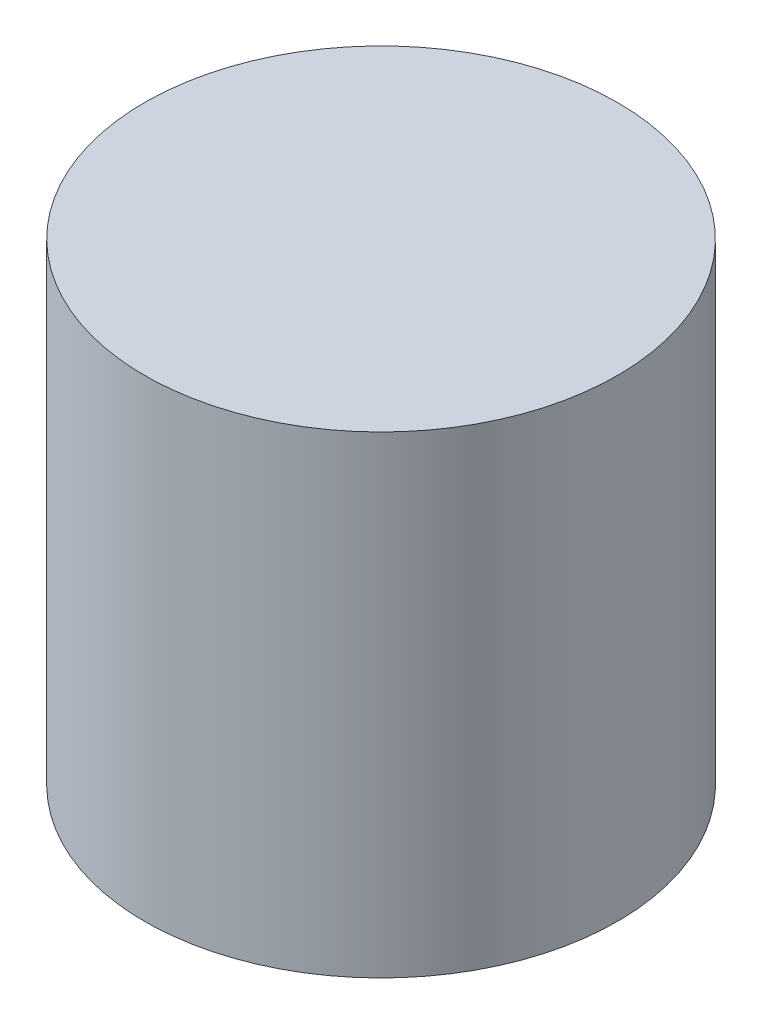
SolidWorks part; units mm, degrees
ref_plane "Front Plane" through (0, 0, 0) normal (0, 0, 1) x (1, 0, 0)
ref_plane "Top Plane" through (0, 0, 0) normal (0, 1, 0) x (1, 0, 0)
ref_plane "Right Plane" through (0, 0, 0) normal (1, 0, 0) x (0, 0, -1)
sketch "Sketch1" plane through (0, 0, 0) normal (0, 1, 0) x (1, 0, 0)
  circle A0 centre (0, 0) radius 38.1
  dimension "D1" = 76.2
extrude "Boss-Extrude1" add sketch "Sketch1" along normal blind 76.2
shell "Shell1" thickness 6.35
sketch "Sketch2" plane through (0, 0, 0) normal (0, -1, 0) x (1, 0, 0)
  circle A0 centre (0, 0) radius 9.525
  dimension "D1" = 19.05
extrude "Cut-Extrude1" cut sketch "Sketch2" against normal up to next
